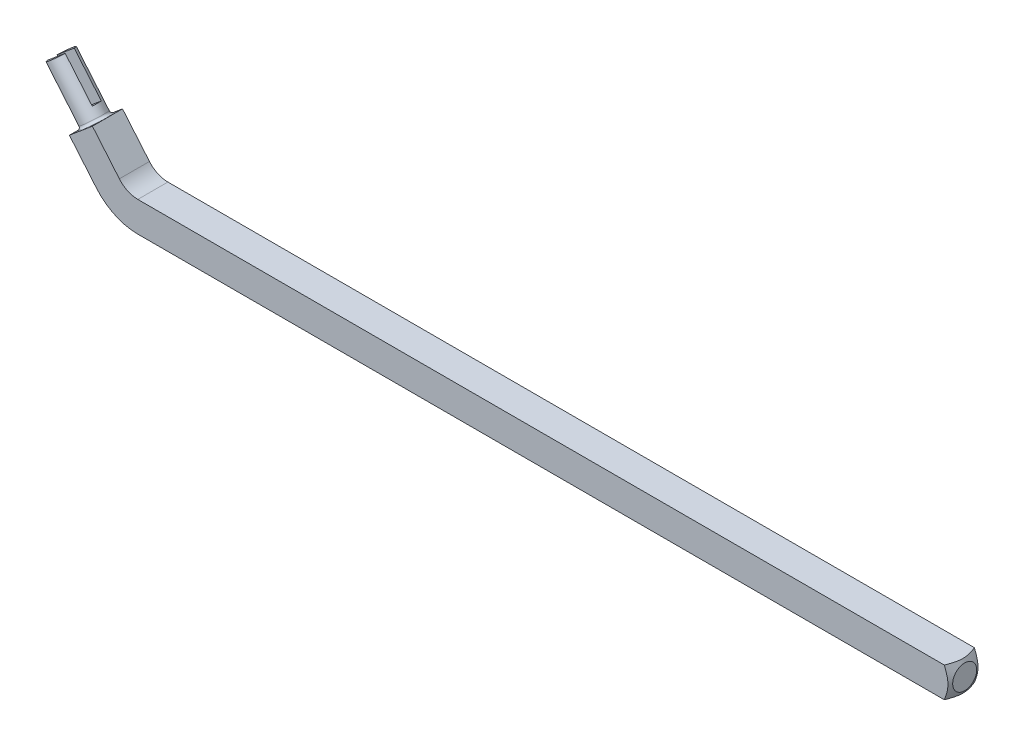
SolidWorks part; units mm, degrees
ref_plane "前视基准面" through (0, 0, 0) normal (0, 0, 1) x (1, 0, 0)
ref_plane "上视基准面" through (0, 0, 0) normal (0, 1, 0) x (1, 0, 0)
ref_plane "右视基准面" through (0, 0, 0) normal (1, 0, 0) x (0, 0, -1)
sketch "草图1" plane through (0, 0, 0) normal (0, 0, 1) x (1, 0, 0)
  line L0 (0, 0) -> (-6.4279, 7.6604) construction
  line L5 (0, 0) -> (138, 0) construction
  line L6 (-1.1658, -2.5) -> (-8.343, 6.0535)
  line L7 (-1.1658, -2.5) -> (138, -2.5)
  line L8 (1.1658, 2.5) -> (-4.5128, 9.2674)
  line L9 (1.1658, 2.5) -> (138, 2.5)
  line L10 (-8.343, 6.0535) -> (-4.5128, 9.2674)
  line L11 (138, 2.5) -> (138, -2.5)
  dimension "D1" = 130
  dimension "D2" = 138
  dimension "D3" = 10
  dimension "D4" = 2.5
  dimension "D5" = 2.5
extrude "凸台-拉伸1" add sketch "草图1" along normal blind 2.5 and the other way blind 2.5
sketch "草图2" plane through (138, 0, 0) normal (1, 0, 0) x (0, 0, -1)
  circle A0 centre (0, 0) radius 2
  dimension "D1" = 4
extrude "切除-拉伸1" cut sketch "草图2" against normal blind 2.5 draft 60 flip side to cut contours A0
fillet "圆角2" radius 4 1 edges at (1.1658, 2.5, 0)
fillet "圆角3" radius 9 1 edges at (-1.1658, -2.5, 0)
sketch "草图3" plane through (-6.4279, 7.6604, 0) normal (-0.6428, 0.766, 0) x (0.766, 0.6428, 0)
  circle A0 centre (0, 0) radius 2
  dimension "D1" = 4
extrude "凸台-拉伸2" add sketch "草图3" along normal blind 9
sketch "草图4" plane through (-12.213, 14.5548, 0) normal (-0.6428, 0.766, 0) x (0.766, 0.6428, 0)
  line L1 (-13.4672, -0.75) -> (13.4672, -0.75)
  line L2 (-13.4672, -0.75) -> (-13.4672, 0.75)
  line L3 (-13.4672, 0.75) -> (13.4672, 0.75)
  line L4 (13.4672, -0.75) -> (13.4672, 0.75)
  line L5 (-13.4672, -0.75) -> (13.4672, 0.75) construction
  line L6 (-13.4672, 0.75) -> (13.4672, -0.75) construction
  point P0 (0, 0)
  dimension "1.5" = 1.5
extrude "切除-拉伸2" cut sketch "草图4" against normal blind 7
fillet "圆角4" radius 0.5 1 edges at (-7.96, 6.3749, 0)
